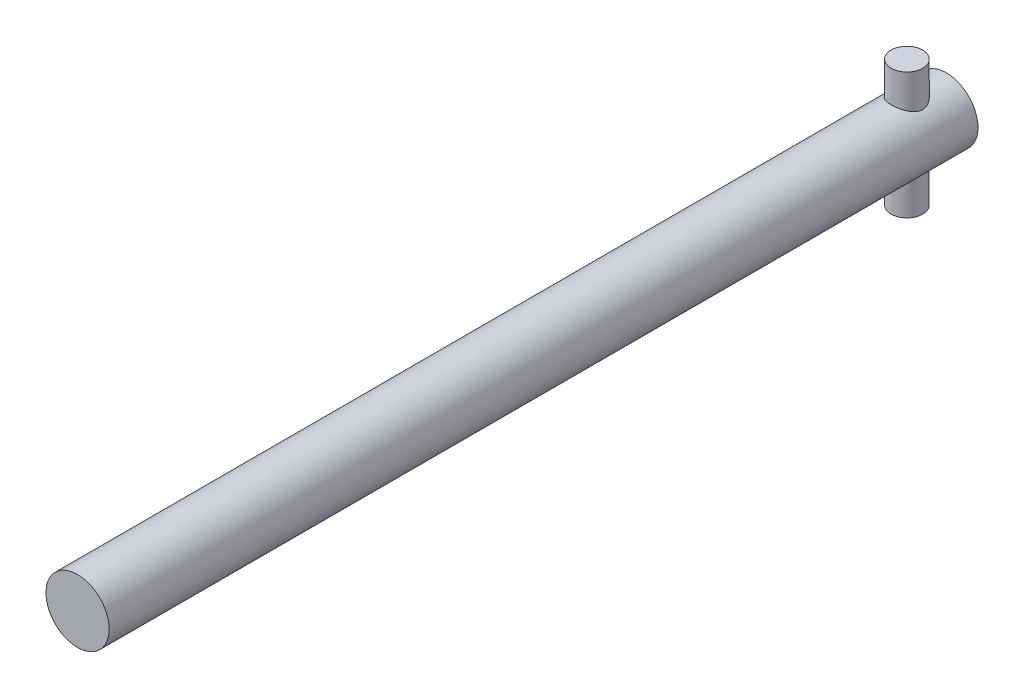
SolidWorks part; units mm, degrees
ref_plane "Front Plane" through (0, 0, 0) normal (0, 0, 1) x (1, 0, 0)
ref_plane "Top Plane" through (0, 0, 0) normal (0, 1, 0) x (1, 0, 0)
ref_plane "Right Plane" through (0, 0, 0) normal (1, 0, 0) x (0, 0, -1)
sketch "Sketch1" plane through (0, 0, 0) normal (0, 0, 1) x (1, 0, 0)
  circle A0 centre (0, 0) radius 4
  dimension "D1" = 8
extrude "Boss-Extrude1" add sketch "Sketch1" along normal blind 110
sketch "Sketch2" plane through (0, 0, 0) normal (0, 1, 0) x (1, 0, 0)
  line L0 (-4, -110) -> (4, -110) construction
  circle A0 centre (0, -5) radius 2
  dimension "D1" = 4
  dimension "D2" = 105
extrude "Boss-Extrude2" add sketch "Sketch2" along normal blind 8 and the other way blind 8
